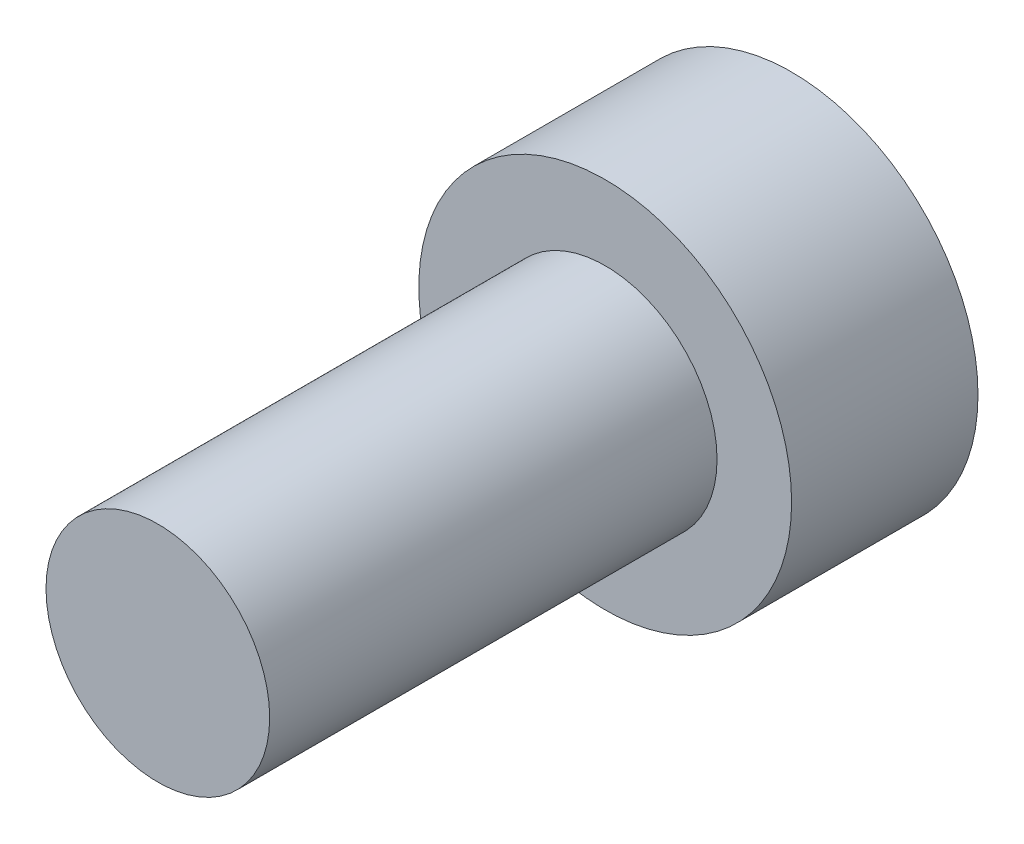
SolidWorks part; units mm, degrees
material "Chrome Stainless Steel"
ref_plane "Front Plane" through (0, 0, 0) normal (0, 0, 1) x (1, 0, 0)
ref_plane "Top Plane" through (0, 0, 0) normal (0, 1, 0) x (1, 0, 0)
ref_plane "Right Plane" through (0, 0, 0) normal (1, 0, 0) x (0, 0, -1)
sketch "Sketch1" plane through (0, 0, 0) normal (0, 0, 1) x (1, 0, 0)
  circle A0 centre (0, 0) radius 2.5
  circle A1 centre (0, 0) radius 1.5
  dimension "D1" = 5
  dimension "D2" = 3
extrude "Boss-Extrude3" add sketch "Sketch1" against normal blind 2.5 contours A0 A1 | A1 region at (-2.4293, 0, 0) region at (0, 0, 0)
extrude "Boss-Extrude4" add sketch "Sketch1<3>" along normal blind 6 contours A1 region at (0, 0, 0)
sketch "Sketch1<3>" plane through (0, 0, 0) normal (0, 0, 1) x (1, 0, 0) same geometry as "Sketch1"
